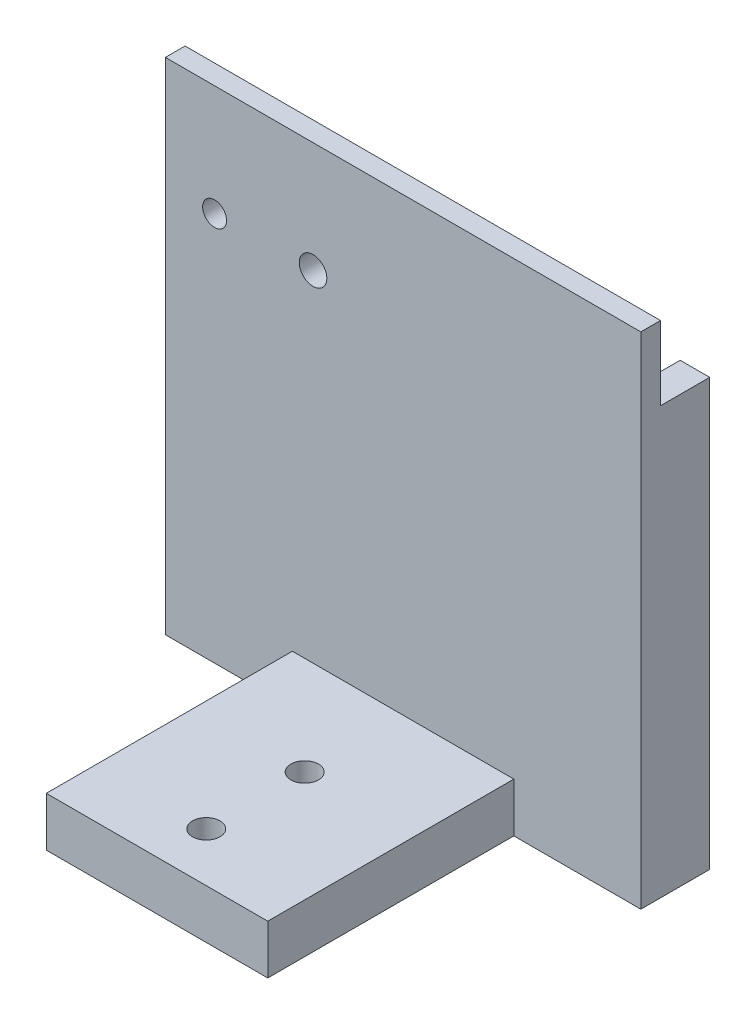
SolidWorks part; units mm, degrees
ref_plane "Front Plane" through (0, 0, 0) normal (0, 0, 1) x (1, 0, 0)
ref_plane "Top Plane" through (0, 0, 0) normal (0, 1, 0) x (1, 0, 0)
ref_plane "Right Plane" through (0, 0, 0) normal (1, 0, 0) x (0, 0, -1)
sketch "Sketch1" plane through (0, 0, 0) normal (0, 0, 1) x (1, 0, 0)
  line L0 (-17.15, 21.15) -> (17.15, 21.15) construction
  line L1 (21.15, -21.15) -> (-21.15, -21.15)
  line L2 (21.15, -21.15) -> (21.15, 21.15)
  line L3 (21.15, 21.15) -> (-21.15, 21.15)
  line L4 (-21.15, -21.15) -> (-21.15, 21.15)
  line L5 (-21.15, -17.15) -> (-21.15, 17.15) construction
  line L6 (21.15, 17.15) -> (21.15, -17.15) construction
  line L7 (17.15, -21.15) -> (-17.15, -21.15) construction
  line L9 (24.15, -22.15) -> (-24.15, -22.15)
  line L10 (24.15, -22.15) -> (24.15, 21.15)
  line L11 (24.15, 21.15) -> (-24.15, 21.15)
  line L12 (-24.15, -22.15) -> (-24.15, 21.15)
  point P16 (-21.15, 0)
  dimension "D1" = 0
  dimension "D2" = 0
  dimension "D3" = 0
  dimension "D4" = 0
  dimension "D5" = 3
  dimension "D6" = 3
  dimension "D7" = 1
  dimension "D8" = 0
extrude "Boss-Extrude1" add sketch "Sketch1" along normal blind 2 contours L4 L1 L2 L3 | L12 L9 L10 L11 L2 L1 L4 region at (21.7987, 0, 0) region at (0, 0, 0)
extrude "Boss-Extrude2" add sketch "Sketch1<3>" against normal blind 5 contours L12 L9 L10 L11 L2 L1 L4 region at (21.7987, 0, 0)
sketch "Sketch1<3>" plane through (0, 0, 0) normal (0, 0, 1) x (1, 0, 0) same geometry as "Sketch1"
sketch "Sketch2" plane through (0, 0, 2) normal (0, 0, 1) x (1, 0, 0)
  line L0 (24.15, -22.15) -> (-24.15, -22.15) construction
  line L1 (11.25, -22.15) -> (-11.25, -22.15)
  line L2 (11.25, -22.15) -> (11.25, -17.15)
  line L3 (11.25, -17.15) -> (-11.25, -17.15)
  line L4 (-11.25, -22.15) -> (-11.25, -17.15)
  line L5 (24.15, -22.15) -> (24.15, 21.15) construction
  dimension "D1" = 22.5
  dimension "D2" = 12.9
  dimension "D3" = 5
extrude "Boss-Extrude3" add sketch "Sketch2" along normal blind 25
sketch "Sketch3" plane through (0, 0, 2) normal (0, 0, 1) x (1, 0, 0)
  line L0 (-134.7739, 28.649) -> (-80.2739, 28.649) construction
  line L1 (-24.15, 6.149) -> (24.15, 6.149)
  line L2 (-24.15, 6.149) -> (-24.15, 28.649)
  line L3 (-24.15, 28.649) -> (24.15, 28.649)
  line L4 (24.15, 6.149) -> (24.15, 28.649)
  line L5 (24.15, -22.15) -> (24.15, 21.15) construction
  line L6 (-24.15, -22.15) -> (-24.15, 21.15) construction
  circle A0 centre (-19.15, 17.399) radius 1.2149
  circle A1 centre (-9.15, 17.399) radius 1.4
  dimension "D5" = 10
  dimension "D6" = 5
  dimension "D7" = 2.8
  dimension "D8" = 11.25
  dimension "D9" = 11.25
  dimension "D1" = 0
  dimension "D2" = 22.5
  dimension "D3" = 0
  dimension "D4" = 0
extrude "Boss-Extrude4" add sketch "Sketch3" against normal blind 2
sketch "Sketch4" plane through (0, -17.15, 0) normal (0, 1, 0) x (1, 0, 0)
  line L0 (11.25, -27) -> (-11.25, -27) construction
  line L1 (-11.25, -27) -> (-11.25, -2) construction
  circle A0 centre (0, -12) radius 1.4
  circle A1 centre (0, -22) radius 1.4
  dimension "D2" = 10
  dimension "D3" = 2.8
  dimension "D4" = 2.8
  dimension "D5" = 11.25
  dimension "D6" = 11.25
  dimension "D1" = 5
extrude "Cut-Extrude1" cut sketch "Sketch4" against normal through all
extrude "Cut-Extrude2" cut sketch "Sketch3<2>" against normal blind 2 contours A1 | A0 region at (-9.15, 17.399, 2)
sketch "Sketch3<2>" plane through (0, 0, 2) normal (0, 0, 1) x (1, 0, 0) same geometry as "Sketch3"
